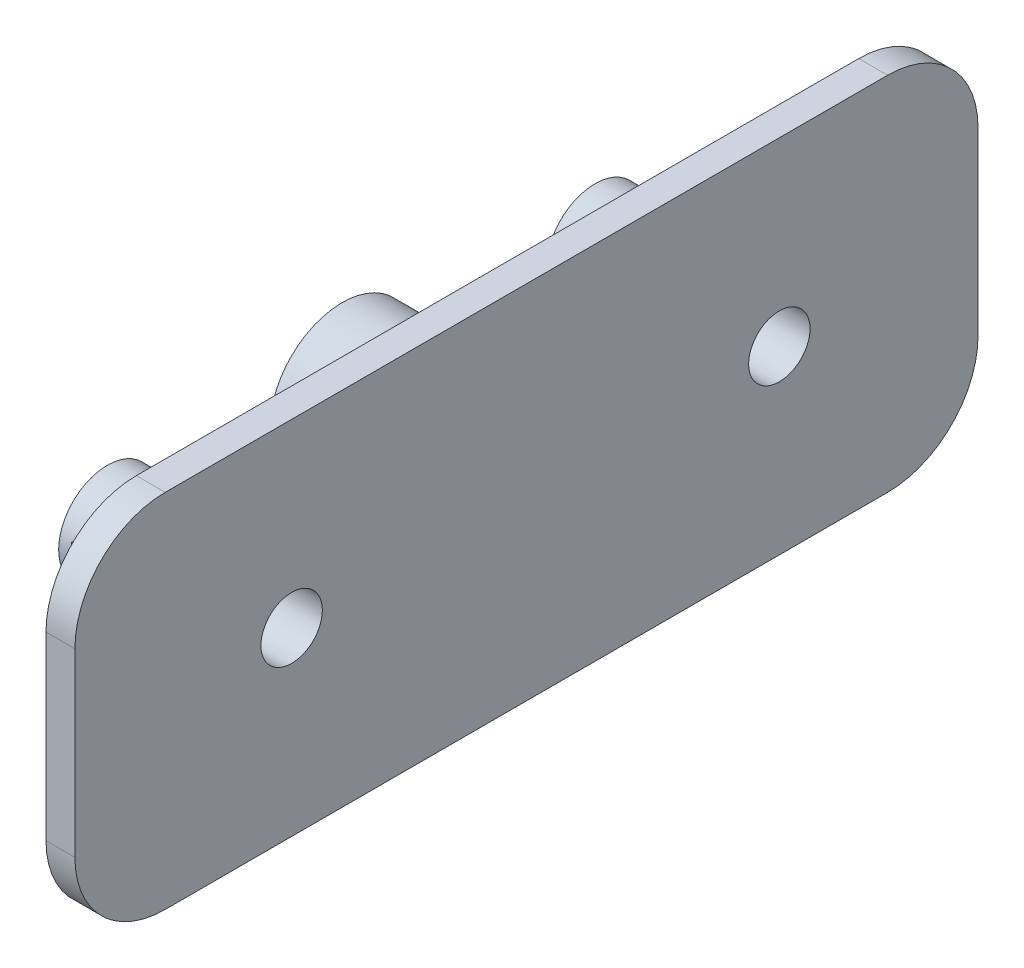
SolidWorks part; units mm, degrees
ref_plane "Front Plane" through (0, 0, 0) normal (0, 0, 1) x (1, 0, 0)
ref_plane "Top Plane" through (0, 0, 0) normal (0, 1, 0) x (1, 0, 0)
ref_plane "Right Plane" through (0, 0, 0) normal (1, 0, 0) x (0, 0, -1)
sketch "Sketch1" plane through (0, 0, 0) normal (1, 0, 0) x (0, 0, -1)
  circle A0 centre (0, 0) radius 3
  circle A2 centre (0, 0) radius 4
  dimension "D1" = 6
  dimension "D2" = 8
extrude "Boss-Extrude1" add sketch "Sketch1" along normal blind 5
sketch "Sketch2" plane through (5, 0, 0) normal (1, 0, 0) x (0, 0, -1)
  line L1 (-20, -5) -> (20, -5)
  line L2 (-20, -5) -> (-20, 5)
  line L3 (-20, 5) -> (20, 5)
  line L4 (20, -5) -> (20, 5)
  line L5 (-20, -5) -> (20, 5) construction
  line L6 (-20, 5) -> (20, -5) construction
  circle A0 centre (0, 0) radius 3
  point P0 (0, 0)
  dimension "D1" = 10
  dimension "D2" = 40
extrude "Boss-Extrude2" add sketch "Sketch2" along normal blind 3.6
sketch "Sketch7" plane through (8.6, 0, 0) normal (1, 0, 0) x (0, 0, -1)
  line L1 (25, -10) -> (-25, -10)
  line L2 (25, -10) -> (25, 10)
  line L3 (25, 10) -> (-25, 10)
  line L4 (-25, -10) -> (-25, 10)
  line L5 (25, -10) -> (-25, 10) construction
  line L6 (25, 10) -> (-25, -10) construction
  point P0 (0, 0)
  dimension "D1" = 50
  dimension "D2" = 20
extrude "Boss-Extrude3" add sketch "Sketch7" along normal blind 1.6
hole_wizard "M3 Clearance Hole1" positions "Sketch5" profile "Sketch6" hole size "M3" standard "ANSI Metric"
sketch "Sketch5" plane through (5, 0, 0) normal (-1, 0, 0) x (0, 0, 1)
  point P0 (-14, 0)
  point P2 (13, 0)
  dimension "D1" = 14
  dimension "D2" = 13
sketch "Sketch6" plane through (5, 0, -14) normal (0, 1, 0) x (0, 0, 1)
  line L0 (0, 0) -> (0, 13.0215)
  line L1 (0, 13.0215) -> (1.7, 12)
  line L2 (1.7, 12) -> (1.7, 0)
  line L5 (1.7, 0) -> (0, 0)
  line L10 (0, 13.0215) -> (-1.7, 12) construction
  line L11 (0, -6.35) -> (0, 107.95) construction
  dimension "Hole Dia." = 3.4
  dimension "Hole Depth" = 12
  dimension "Drill Angle" = 118
sketch "Sketch8" plane through (5, 0, 0) normal (-1, 0, 0) x (0, 0, 1)
  circle A0 centre (-14, 0) radius 1.7
  circle A1 centre (-14, 0) radius 2.7
  circle A2 centre (13, 0) radius 1.7
  circle A3 centre (13, 0) radius 2.7
  circle A4 centre (-14, 0) radius 1.7 construction
  circle A5 centre (13, 0) radius 1.7 construction
  dimension "D1" = 5.4
  dimension "D2" = 5.4
extrude "Boss-Extrude4" add sketch "Sketch8" along normal blind 5
fillet "Fillet2" radius 5 4 edges at (9.4, 10, -25) (9.4, -10, -25) (9.4, -10, 25) (9.4, 10, 25)
